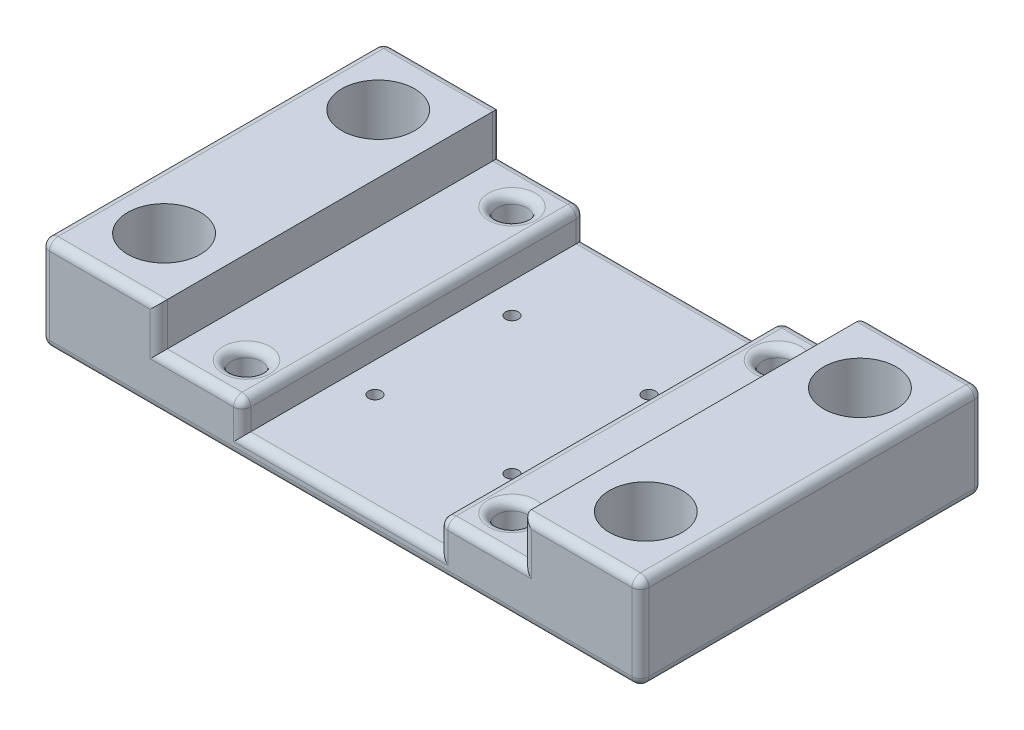
SolidWorks part; units mm, degrees
ref_plane "Płaszczyzna przednia" through (0, 0, 0) normal (0, 0, 1) x (1, 0, 0)
ref_plane "Płaszczyzna górna" through (0, 0, 0) normal (0, 1, 0) x (1, 0, 0)
ref_plane "Płaszczyzna prawa" through (0, 0, 0) normal (1, 0, 0) x (0, 0, -1)
sketch "Szkic1" plane through (0, 0, 0) normal (0, 1, 0) x (1, 0, 0)
  line L1 (-35, 20) -> (35, 20)
  line L2 (-35, 20) -> (-35, -20)
  line L3 (-35, -20) -> (35, -20)
  line L4 (35, 20) -> (35, -20)
  line L5 (-35, 20) -> (35, -20) construction
  line L6 (-35, -20) -> (35, 20) construction
  point P0 (0, 0)
  dimension "D1" = 40
  dimension "D2" = 70
extrude "Dodanie-wyciągnięcie1" add sketch "Szkic1" along normal blind 6
sketch "Szkic2" plane through (0, 6, 0) normal (0, 1, 0) x (1, 0, 0)
  line L0 (-35, -20) -> (35, -20) construction
  line L1 (-35, 20) -> (-21.25, 20)
  line L2 (-35, 20) -> (-35, -20)
  line L3 (-35, -20) -> (-21.25, -20)
  line L4 (-21.25, 20) -> (-21.25, -20)
  line L6 (35, 20) -> (21.25, 20)
  line L7 (35, 20) -> (35, -20)
  line L8 (35, -20) -> (21.25, -20)
  line L9 (21.25, 20) -> (21.25, -20)
  dimension "D1" = 42.5
extrude "Dodanie-wyciągnięcie2" add sketch "Szkic2" along normal blind 5
sketch "Szkic3" plane through (0, 6, 0) normal (0, 1, 0) x (1, 0, 0)
  line L0 (21.25, 20) -> (-21.25, 20) construction
  line L1 (-11.5, 20) -> (11.5, 20)
  line L2 (-11.5, 20) -> (-11.5, -20)
  line L3 (-11.5, -20) -> (11.5, -20)
  line L4 (11.5, 20) -> (11.5, -20)
  line L5 (-21.25, -20) -> (21.25, -20) construction
  point P6 (0, -20)
  dimension "D1" = 23
extrude "Wytnij-wyciągnięcie1" cut sketch "Szkic3" against normal blind 3.5
hole_wizard "Otwory ustalające Ø6.0mm1" positions "Szkic4" profile "Szkic5" hole size "Ø6.0" standard "Ansi Metric" end condition through all
sketch "Szkic4" plane through (0, 11, 0) normal (0, 1, 0) x (1, 0, 0)
  line L1 (35, 20) -> (21.25, 20) construction
  line L2 (-21.25, 20) -> (-35, 20) construction
  line L3 (0, 0) -> (33.1522, 0) construction
  point P0 (-28.125, 12.5)
  point P2 (-28.125, -12.5)
  point P4 (28.125, 12.5)
  point P6 (28.125, -12.5)
  point P17 (28.125, 20)
  point P21 (-28.125, 20)
  dimension "D1" = 25
sketch "Szkic5" plane through (-28.125, 11, -12.5) normal (1, 0, 0) x (0, 0, 1)
  line L0 (0, 0) -> (0, 11)
  line L1 (0, 11) -> (4.25, 11)
  line L2 (4.25, 11) -> (4.25, 0)
  line L5 (4.25, 0) -> (0, 0)
  line L11 (0, -6.35) -> (0, 107.95) construction
  dimension "Średnica otworu na wylot" = 8.5
  dimension "Głębokość otworu na wylot" = 11
sketch "Szkic6" plane through (0, 0, 0) normal (0, -1, 0) x (-1, 0, 0)
  arc A0 (-15.5, -14.25) -> (-15.5, -16.75) centre (-15.5, -15.5) ccw construction
  arc A1 (15.5, -14.25) -> (15.5, -16.75) centre (15.5, -15.5) ccw construction
  arc A2 (15.5, 16.75) -> (15.5, 14.25) centre (15.5, 15.5) ccw construction
  arc A3 (-15.5, 16.75) -> (-15.5, 14.25) centre (-15.5, 15.5) ccw construction
  arc A4 (-15.5, 14.25) -> (-15.5, 16.75) centre (-15.5, 15.5) ccw construction
  arc A5 (-15.5, -14.25) -> (-15.5, -16.75) centre (-15.5, -15.5) ccw construction
  arc A6 (15.5, -14.25) -> (15.5, -16.75) centre (15.5, -15.5) ccw construction
  arc A7 (15.5, 16.75) -> (15.5, 14.25) centre (15.5, 15.5) ccw construction
  arc A8 (-15.5, 16.75) -> (-15.5, 14.25) centre (-15.5, 15.5) ccw construction
  arc A9 (-15.5, 14.25) -> (-15.5, 16.75) centre (-15.5, 15.5) ccw construction
  circle A10 centre (15.5, 15.5) radius 1.75
  circle A11 centre (-15.5, 15.5) radius 1.75
  circle A12 centre (-15.5, -15.5) radius 1.75
  circle A13 centre (15.5, -15.5) radius 1.75
  dimension "D1" = 3.5
extrude "Wytnij-wyciągnięcie2" cut sketch "Szkic6" against normal through all
chamfer "Sfazowanie1" distance 2 angle 45 4 edges at (15.5, 0, 13.75) (15.5, 0, -17.25) (-15.5, 0, -17.25) (-15.5, 0, 13.75)
hole_wizard "Otwory ustalające Ø1.5mm1" positions "Szkic10" profile "Szkic9" hole size "Ø1.5" standard "Ansi Metric" end condition through all
sketch "Szkic10" plane through (0, 2.5, 0) normal (0, 1, 0) x (1, 0, 0)
  point P0 (8, -8)
  dimension "D1" = 8
  dimension "D2" = 8
sketch "Szkic9" plane through (8, 2.5, 8) normal (1, 0, 0) x (0, 0, 1)
  line L0 (0, 0) -> (0, 2.5)
  line L1 (0, 2.5) -> (0.75, 2.5)
  line L2 (0.75, 2.5) -> (0.75, 0)
  line L5 (0.75, 0) -> (0, 0)
  line L11 (0, -6.35) -> (0, 107.95) construction
  dimension "Średnica otworu na wylot" = 1.5
  dimension "Głębokość otworu na wylot" = 2.5
pattern_linear "Szyk liniowy1" count 2 spacing 16 along (-1, 0, 0) count 2 spacing 16 along (0, 0, -1) of "Otwory ustalające Ø1.5mm1"
fillet "Zaokrąglenie1" radius 1 46 edges at (-8, 0, 8.75) (8, 0, 8.75) (-15.5, 6, -13.75) (15.5, 6, -13.75) (15.5, 6, 17.25) (-15.5, 6, 17.25) (-28.125, 0, -8.25) (-28.125, 0, 16.75) (28.125, 0, -8.25) (28.125, 0, 16.75) (-11.5, 6, 0) (11.5, 6, 0) (0, 2.5, 20) (0, 2.5, -20) (-11.5, 4.25, 20) (11.5, 4.25, 20) (11.5, 4.25, -20) (-11.5, 4.25, -20) (35, 11, 0) (28.125, 11, -20) (28.125, 11, 20) (21.25, 8.5, 20) (21.25, 8.5, -20) (-35, 11, 0) (-28.125, 11, 20) (-28.125, 11, -20) (-21.25, 8.5, -20) (-21.25, 8.5, 20) (35, 0, 0) (0, 0, -20) (-35, 0, 0) (0, 0, 20) (-16.375, 6, -20) (16.375, 6, -20) (16.375, 6, 20) (-16.375, 6, 20) (35, 5.5, 20) (-35, 5.5, 20) (35, 5.5, -20) (-15.5, 0, 19.25) (-15.5, 0, -11.75) (15.5, 0, -11.75) (15.5, 0, 19.25) (8, 0, -7.25) (-8, 0, -7.25) (-35, 5.5, -20)
